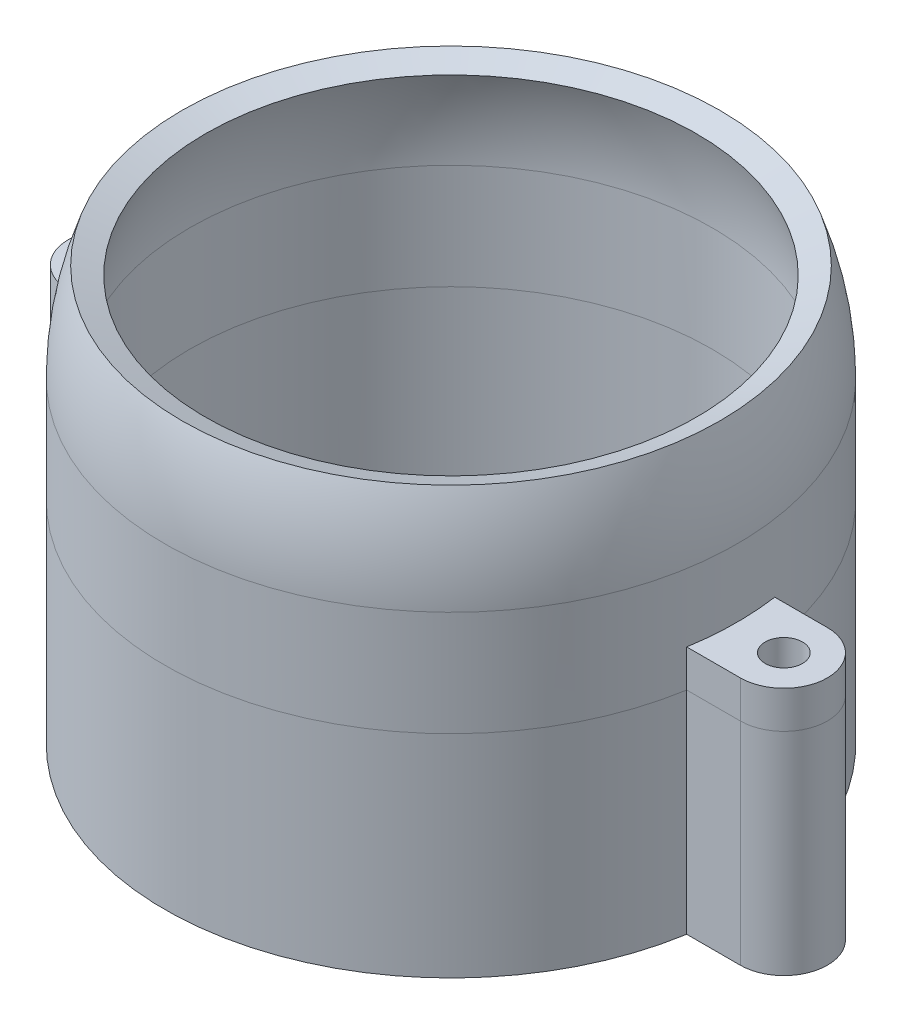
SolidWorks part; units mm, degrees
material "ABS"
ref_plane "Front Plane" through (0, 0, 0) normal (0, 0, 1) x (1, 0, 0)
ref_plane "Top Plane" through (0, 0, 0) normal (0, 1, 0) x (1, 0, 0)
ref_plane "Right Plane" through (0, 0, 0) normal (1, 0, 0) x (0, 0, -1)
sketch "Sketch4" plane through (0, 0, 0) normal (0, 0, 1) x (1, 0, 0)
  line L0 (-21, 4) -> (-21, 25.4499)
  line L1 (-21, 25.4499) -> (0, 25.4499) construction
  line L2 (0, 25.4499) -> (0, 0) construction
  line L3 (0, 0) -> (-21, 0) construction
  line L4 (-23, 0) -> (-23, 25.4499)
  line L5 (-21, 0) -> (-23, 0)
  line L6 (-19.7335, 32.6324) -> (-21.6129, 33.3164)
  line L7 (-9.1577, 4) -> (0, 4)
  line L8 (0, 4) -> (0, 0)
  line L9 (0, 0) -> (-21, 0)
  line L10 (-21, 0) -> (-21, 25.4499) construction
  line L11 (-9.1577, 4) -> (-9.1577, 2)
  line L12 (-9.1577, 2) -> (-21, 2)
  line L13 (-21, 2) -> (-21, 4)
  line L14 (-21, 4) -> (-21, 2)
  circle A0 centre (0, 25.4499) radius 20 construction
  arc A1 (-21, 25.4499) -> (-19.7335, 32.6324) centre (0, 25.4499) cw
  arc A2 (-23, 25.4499) -> (-21.6129, 33.3164) centre (0, 25.4499) cw
  circle A3 centre (-5, 3) radius 3 construction
  dimension "D3" = 40
  dimension "D6" = 6
  dimension "D1" = 21
  dimension "D2" = 5
  dimension "D4" = 20
  dimension "D7" = 4
  dimension "D8" = 2
  dimension "D5" = 2
revolve "Revolve1" add sketch "Sketch4" angle 360 about L2 region at (-21.4048, 3, 0)
sketch "Sketch5" plane through (0, 0, 0) normal (0, -1, 0) x (-1, 0, 0)
  line L0 (0, -23) -> (0, 23) construction
  line L1 (23, 0) -> (-23, 0) construction
  line L2 (27, -3.75) -> (22.6922, -3.75)
  line L3 (27, 3.25) -> (22.7692, 3.25)
  line L13 (-27, 3.25) -> (-22.7692, 3.25)
  line L14 (-27, -3.75) -> (-22.6922, -3.75)
  circle A0 centre (0, 0) radius 23 construction
  circle A1 centre (27, -0.25) radius 1.5
  arc A2 (27, -3.75) -> (27, 3.25) centre (27, -0.25) ccw
  arc A3 (22.7692, 3.25) -> (22.6922, -3.75) centre (0, 0) cw
  circle A19 centre (-27, -0.25) radius 1.5
  arc A20 (-27, -3.75) -> (-27, 3.25) centre (-27, -0.25) cw
  arc A21 (-22.7692, 3.25) -> (-22.6922, -3.75) centre (0, 0) ccw
  dimension "D1" = 3
  dimension "D2" = 2
  dimension "D3" = 27
extrude "Boss-Extrude3" add sketch "Sketch5" against normal blind 20
ref_axis "Axis1" through (-33.825, 0, 0) along (1, 0, 0)
ref_plane "Plane1" through (0, 0, 0) normal (0, 0, -1) x (1, 0, 0)
sketch "Sketch7" plane through (0, 0, 0) normal (0, 0, -1) x (1, 0, 0)
  line L0 (-33.825, 0) -> (33.825, 0) construction
  line L1 (-5, 0) -> (-8.1, 0)
  line L2 (-8.1, -3.1) -> (-8.1, 0)
  line L3 (-5, -6.2) -> (-5, 0)
  arc A0 (-8.1, -3.1) -> (-5, -6.2) centre (-5, -3.1) ccw
  dimension "D1" = 6.2
  dimension "D2" = 5
revolve "Cut-Revolve1" cut sketch "Sketch7" angle 360 about L3
ref_axis "Axis2" through (0, 34.9822, 0) along (0, -1, 0)
pattern_circular "CirPattern1" count 3 every 120 about axis through (0, 34.9822, 0) along (0, -1, 0) of "Cut-Revolve1"
ref_plane "Plane2" through (0, 17, 0) normal (0, -1, 0) x (-1, 0, 0)
split "Split1" trim tools "Plane2" bodies to split 106 resulting bodies 107 108
